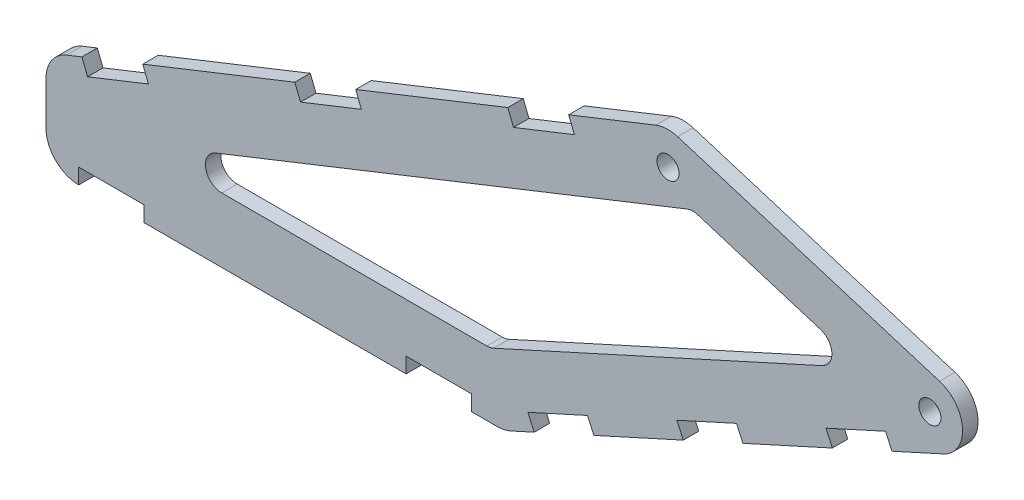
SolidWorks part; units mm, degrees
material "Custom Plastic"
ref_plane "Front Plane" through (0, 0, 0) normal (0, 0, 1) x (1, 0, 0)
ref_plane "Top Plane" through (0, 0, 0) normal (0, 1, 0) x (1, 0, 0)
ref_plane "Right Plane" through (0, 0, 0) normal (1, 0, 0) x (0, 0, -1)
sketch "Sketch1" plane through (0, 0, 0) normal (0, 0, 1) x (1, 0, 0)
  line L0 (76.2, 0) -> (76.2, 41.0718) construction
  line L1 (0, 0) -> (127, 0) construction
  line L2 (127, 0) -> (127, 25.4) construction
  dimension "D1" = 127
  dimension "D2" = 25.4
  dimension "D3" = 41.0718
  dimension "D4" = 76.2
sketch "Sketch2" plane through (0, 0, 0) normal (0, 0, 1) x (1, 0, 0)
  line L1 (-44.45, -19.05) -> (44.45, -19.05)
  line L2 (78.0719, 47.1396) -> (128.8719, 31.4678)
  line L3 (-44.45, 0) -> (73.8567, 46.9736)
  line L4 (44.45, -19.05) -> (129.625, 19.6179)
  line L5 (-44.45, 0) -> (-44.45, -19.05)
  arc A0 (78.0719, 47.1396) -> (73.8567, 46.9736) centre (76.2, 41.0718) ccw
  arc A1 (129.625, 19.6179) -> (128.8719, 31.4678) centre (127, 25.4) ccw
  point P10 (-44.45, -19.05)
  point P12 (44.45, -19.05)
  point P17 (-44.45, 0)
  point P19 (0, -19.05)
  dimension "D1" = 6.35
  dimension "D5" = 19.05
  dimension "D8" = 88.9
extrude "Base" add sketch "Sketch2" along normal blind 2.9972
hole_wizard "Joint holes" positions "Sketch4" profile "Sketch3" hole size "#8" standard "ANSI Inch"
sketch "Sketch4" plane through (0, 0, 2.9972) normal (0, 0, 1) x (1, 0, 0)
  point P0 (76.2, 41.0718)
  point P3 (127, 25.4)
sketch "Sketch3" plane through (76.2, 41.0718, 2.9972) normal (1, 0, 0) x (0, -1, 0)
  line L0 (0, 0) -> (0, 6.351)
  line L1 (0, 6.351) -> (2.1526, 6.351)
  line L2 (2.1526, 6.351) -> (2.1526, 0)
  line L5 (2.1526, 0) -> (0, 0)
  line L10 (0, 6.351) -> (-2.1526, 6.351) construction
  line L11 (0, -6.35) -> (0, 107.95) construction
  dimension "Hole Dia." = 4.3053
  dimension "Hole Depth" = 6.351
  dimension "Drill Angle" = 180
fillet "Outer fillet" radius 6.35 3 edges at (44.45, -19.05, 1.4986) (-44.45, -19.05, 1.4986) (-44.45, 0, 1.4986)
sketch "Sketch5" plane through (0, 0, 2.9972) normal (0, 0, 1) x (1, 0, 0)
  line L0 (-38.1, -19.05) -> (43.0761, -19.05) construction
  line L1 (-38.1, -19.05) -> (-25.4, -19.05)
  line L2 (-38.1, -19.05) -> (-38.1, -16.0528)
  line L3 (-38.1, -16.0528) -> (-25.4, -16.0528)
  line L4 (-25.4, -19.05) -> (-25.4, -16.0528)
  line L6 (25.4, -19.05) -> (38.1, -19.05)
  line L7 (25.4, -19.05) -> (25.4, -16.0528)
  line L8 (25.4, -16.0528) -> (38.1, -16.0528)
  line L9 (38.1, -19.05) -> (38.1, -16.0528)
  dimension "D1" = 12.7
  dimension "D2" = 25.4
  dimension "D3" = 2.9972
  dimension "D4" = 25.4
extrude "Base plate slots" cut sketch "Sketch5" against normal through all
sketch "Sketch6" plane through (0, 0, 2.9972) normal (0, 0, 1) x (1, 0, 0)
  line L0 (50.2603, -16.4122) -> (49.0214, -13.6831)
  line L1 (45.701, -18.4821) -> (129.625, 19.6179) construction
  line L2 (49.0214, -13.6831) -> (60.5855, -8.4332)
  line L3 (60.5855, -8.4332) -> (61.8245, -11.1623)
  line L4 (50.2603, -16.4122) -> (61.8245, -11.1623)
  line L5 (79.1706, -3.2874) -> (77.9316, -0.5583)
  line L6 (77.9316, -0.5583) -> (89.4957, 4.6916)
  line L7 (89.4957, 4.6916) -> (90.7347, 1.9625)
  line L8 (79.1706, -3.2874) -> (90.7347, 1.9625)
  line L9 (108.0809, 9.8373) -> (106.8419, 12.5664)
  line L10 (106.8419, 12.5664) -> (118.406, 17.8163)
  line L11 (118.406, 17.8163) -> (119.645, 15.0872)
  line L12 (108.0809, 9.8373) -> (119.645, 15.0872)
  arc A0 (43.0761, -19.05) -> (45.701, -18.4821) centre (43.0761, -12.7) ccw construction
  point P4 (44.4189, -18.9064)
  dimension "D1" = 2.9972
  dimension "D2" = 12.7
  dimension "D3" = 6.35
  dimension "D4" = 3
  dimension "D5" = 31.75
extrude "Under plate slots" cut sketch "Sketch6" against normal through all
sketch "Sketch7" plane through (0, 0, 2.9972) normal (0, 0, 1) x (1, 0, 0)
  line L0 (-37.4924, 2.7625) -> (-36.3864, -0.0231)
  line L1 (73.8567, 46.9736) -> (-40.4433, 1.5909) construction
  line L2 (-36.3864, -0.0231) -> (-24.5827, 4.6635)
  line L3 (-24.5827, 4.6635) -> (-25.6888, 7.4491)
  line L4 (-37.4924, 2.7625) -> (-25.6888, 7.4491)
  line L6 (3.8203, 19.1657) -> (4.9263, 16.38)
  line L7 (4.9263, 16.38) -> (16.7299, 21.0667)
  line L8 (16.7299, 21.0667) -> (15.6239, 23.8523)
  line L9 (3.8203, 19.1657) -> (15.6239, 23.8523)
  line L11 (45.133, 35.5689) -> (46.239, 32.7832)
  line L12 (46.239, 32.7832) -> (58.0426, 37.4698)
  line L13 (58.0426, 37.4698) -> (56.9366, 40.2555)
  line L14 (45.133, 35.5689) -> (56.9366, 40.2555)
  dimension "D1" = 2.9972
  dimension "D2" = 12.7
  dimension "D3" = 3.175
  dimension "D5" = 44.45
  dimension "D4" = 3
extrude "Top plate slots" cut sketch "Sketch7" against normal through all
sketch "Sketch8" plane through (0, 0, 2.9972) normal (0, 0, 1) x (1, 0, 0)
  line L0 (-26.9576, -6.5278) -> (80.9031, 36.2982)
  line L1 (-26.9576, -6.5278) -> (41.7406, -6.5278)
  line L2 (41.7406, -6.5278) -> (113.7523, 26.1643)
  line L3 (3.8203, 19.1657) -> (-25.6888, 7.4491) construction
  line L4 (-25.4, -19.05) -> (25.4, -19.05) construction
  line L5 (61.8245, -11.1623) -> (79.1706, -3.2874) construction
  line L6 (4.9263, 16.38) -> (16.7299, 21.0667) construction
  line L7 (38.1, -16.0528) -> (25.4, -16.0528) construction
  line L8 (60.5855, -8.4332) -> (49.0214, -13.6831) construction
  line L9 (80.9031, 36.2982) -> (113.7523, 26.1643)
  line L10 (128.8719, 31.4678) -> (78.0719, 47.1396) construction
  dimension "D1" = 9.525
  dimension "D2" = 9.525
  dimension "D3" = 9.525
  dimension "D4" = 9.525
extrude "Inner hole" cut sketch "Sketch8" against normal through all
fillet "Inner fillet" radius 3.175 4 edges at (-26.9576, -6.5278, 1.4986) (113.7523, 26.1643, 1.4986) (41.7406, -6.5278, 1.4986) (80.9031, 36.2982, 1.4986)
